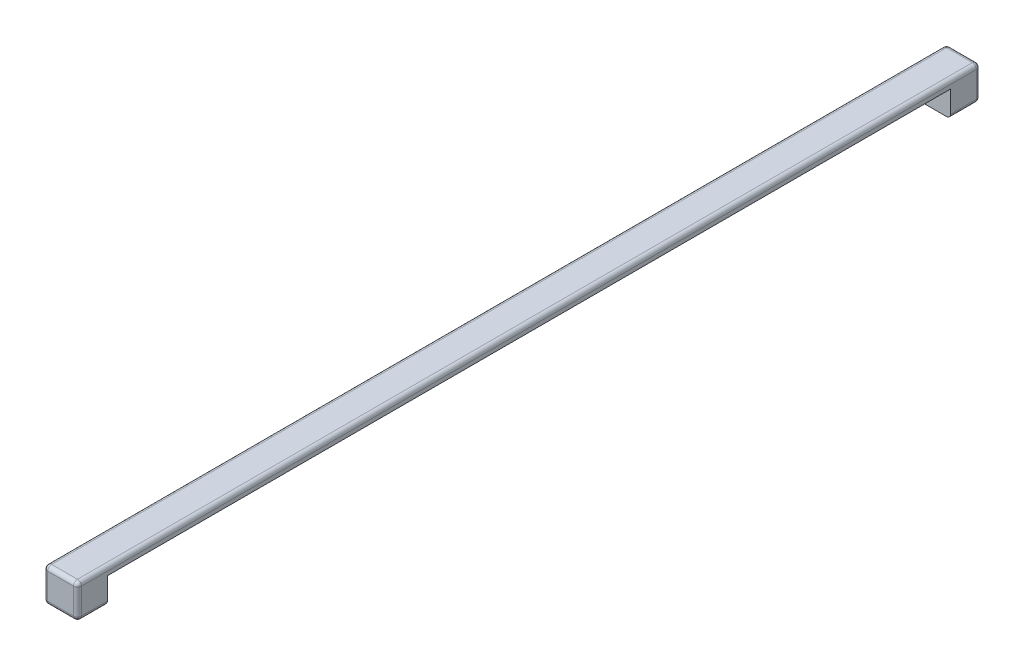
SolidWorks part; units mm, degrees
material "7075-T6, Plate (SS)"
ref_plane "Front Plane" through (0, 0, 0) normal (0, 0, 1) x (1, 0, 0)
ref_plane "Top Plane" through (0, 0, 0) normal (0, 1, 0) x (1, 0, 0)
ref_plane "Right Plane" through (0, 0, 0) normal (1, 0, 0) x (0, 0, -1)
sketch "Sketch1" plane through (0, 0, 0) normal (0, 0, 1) x (1, 0, 0)
  line L1 (-4.25, -4.25) -> (4.25, -4.25)
  line L2 (-4.25, -4.25) -> (-4.25, 4.25)
  line L3 (-4.25, 4.25) -> (4.25, 4.25)
  line L4 (4.25, -4.25) -> (4.25, 4.25)
  line L5 (-4.25, -4.25) -> (4.25, 4.25) construction
  line L6 (-4.25, 4.25) -> (4.25, -4.25) construction
  point P0 (0, 0)
  dimension "D1" = 8.5
  dimension "D2" = 8.5
extrude "Boss-Extrude1" add sketch "Sketch1" along normal mid plane 227
fillet "Fillet2" radius 1 12 edges at (0, 4.25, 113.5) (-4.25, 4.25, 0) (-4.25, 0, 113.5) (4.25, 0, 113.5) (4.25, 4.25, 0) (0, 4.25, -113.5) (-4.25, 0, -113.5) (4.25, 0, -113.5) (-4.25, -4.25, 0) (0, -4.25, 113.5) (4.25, -4.25, 0) (0, -4.25, -113.5)
sketch "Sketch2" plane through (0, 0, 0) normal (0, 0, 1) x (1, 0, 0)
  line L0 (4.25, 3.25) -> (4.25, -3.25) construction
  line L1 (4.25, -4.25) -> (-2.25, -4.25)
  line L2 (4.25, -4.25) -> (4.25, 2.25)
  line L3 (4.25, 2.25) -> (-2.25, 2.25)
  line L4 (-2.25, -4.25) -> (-2.25, 2.25)
  line L5 (3.25, -4.25) -> (-3.25, -4.25) construction
  line L6 (-3.25, 4.25) -> (3.25, 4.25) construction
  line L7 (-4.25, -3.25) -> (-4.25, 3.25) construction
  dimension "D1" = 2
  dimension "D2" = 2
extrude "Cut-Extrude1" cut sketch "Sketch2" along normal offset from surface 7.5 and the other way offset from surface 7.5 up to face at (0, 0, 113.5) other way up to face at (0, 0, -113.5)
sketch "Sketch4" [suppressed] plane through (0, 0, 106) normal (0, 0, -1) x (-1, 0, 0)
  circle A0 centre (0, 0) radius 1.5
  dimension "D1" = 3
extrude "Cut-Extrude2" [suppressed] cut sketch "Sketch4" against normal up to surface (7.5 mm away)
sketch "Sketch3" [suppressed] plane through (0, 0, 113.5) normal (0, 0, 1) x (1, 0, 0)
  circle A0 centre (0, 0) radius 1
  dimension "D1" = 2
extrude "Boss-Extrude2" [suppressed] add sketch "Sketch3" along normal blind 2 and the other way blind 10
mirror "Mirror1" [suppressed] about plane through (0, 0, 0) normal (0, 0, 1)
mirror "Mirror2" [suppressed] about plane through (0, 0, 0) normal (0, 0, 1) of bodies 103
